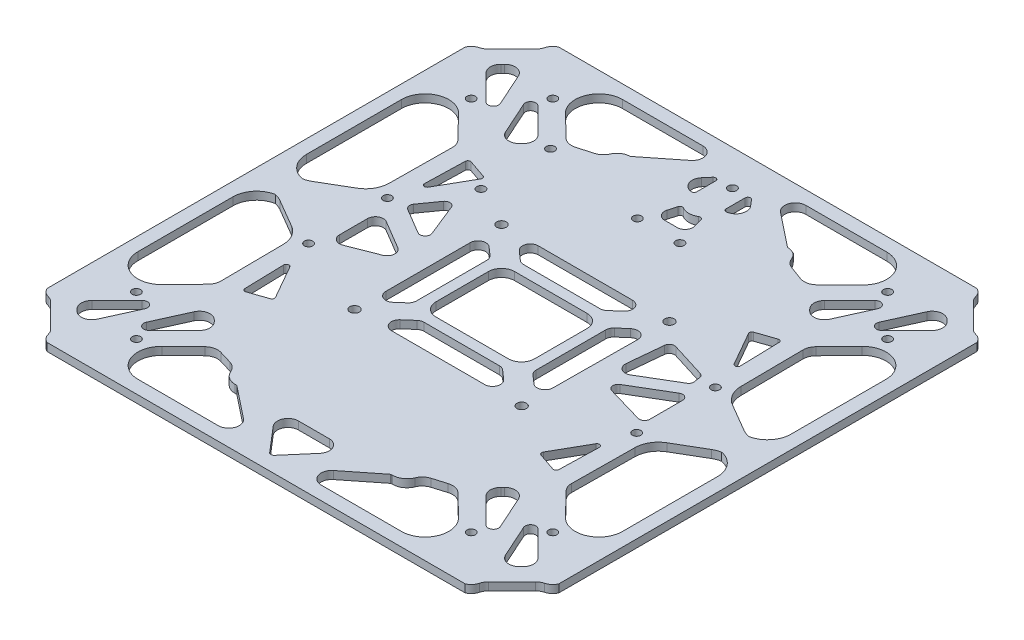
SolidWorks part; units mm, degrees
material "Thornel Mat VMA"
ref_plane "Front Plane" through (0, 0, 0) normal (0, 0, 1) x (1, 0, 0)
ref_plane "Top Plane" through (0, 0, 0) normal (0, 1, 0) x (1, 0, 0)
ref_plane "Right Plane" through (0, 0, 0) normal (1, 0, 0) x (0, 0, -1)
sketch "Sketch2" plane through (0, 0, 0) normal (0, 1, 0) x (1, 0, 0)
  line L1 (-97.5, -97.5) -> (97.5, -97.5)
  line L2 (-97.5, -97.5) -> (-97.5, 97.5)
  line L3 (-97.5, 97.5) -> (97.5, 97.5)
  line L4 (97.5, -97.5) -> (97.5, 97.5)
  line L5 (-97.5, -97.5) -> (97.5, 97.5) construction
  line L6 (-97.5, 97.5) -> (97.5, -97.5) construction
  point P0 (0, 0)
  dimension "D1" = 195
  dimension "D2" = 195
extrude "Boss-Extrude1" add sketch "Sketch2" along normal blind 3
sketch "Sketch3" plane through (0, 3, 0) normal (0, 1, 0) x (1, 0, 0)
  circle A2 centre (47.5, 41.25) radius 1.6
  circle A3 centre (47.5, -41.25) radius 1.6
  circle A4 centre (-47.5, -41.25) radius 1.6
  circle A5 centre (-47.5, 41.25) radius 1.6
  dimension "D3" = 3.2
extrude "Cut-Extrude1" cut sketch "Sketch3" against normal through all both and the other way through all
sketch "Sketch4" plane through (0, 3, 0) normal (0, 1, 0) x (1, 0, 0)
  line L4 (97.5, 97.5) -> (-97.5, 97.5) construction
  circle A0 centre (46.1238, 61.6802) radius 2.11
  circle A3 centre (-61.6802, 46.1238) radius 2.11
  circle A5 centre (-77.9437, 93.5) radius 1.35
  circle A6 centre (-93.5, 77.9437) radius 1.35
  circle A7 centre (-46.1238, 61.6802) radius 2.11
  circle A8 centre (93.5, 77.9437) radius 1.35
  circle A9 centre (77.9437, 93.5) radius 1.35
  circle A10 centre (61.6802, 46.1238) radius 2.11
  circle A11 centre (61.6802, -46.1238) radius 2.11
  circle A12 centre (77.9437, -93.5) radius 1.35
  circle A13 centre (93.5, -77.9437) radius 1.35
  circle A14 centre (-46.1238, -61.6802) radius 2.11
  circle A15 centre (-93.5, -77.9437) radius 1.35
  circle A16 centre (-77.9437, -93.5) radius 1.35
  circle A17 centre (-61.6802, -46.1238) radius 2.11
  circle A18 centre (46.1238, -61.6802) radius 2.11
  dimension "D1" = 2.7
  dimension "D3" = 4.22
  dimension "D6" = 4
extrude "Cut-Extrude2" cut sketch "Sketch4" against normal through all both and the other way through all
sketch "Sketch5" plane through (0, 3, 0) normal (0, 1, 0) x (1, 0, 0)
  circle A1 centre (30, 70) radius 2
  circle A2 centre (15, 70) radius 2
  circle A3 centre (-15, 70) radius 2
  circle A4 centre (-30, 70) radius 2
  circle A5 centre (-30, -70) radius 2
  circle A6 centre (-15, -70) radius 2
  circle A7 centre (15, -70) radius 2
  circle A8 centre (30, -70) radius 2
  dimension "D3" = 4
  dimension "D4" = 4
  dimension "D1" = 4
  dimension "D2" = 4
  dimension "D5" = 4
  dimension "D6" = 4
  dimension "D7" = 4
  dimension "D8" = 4
extrude "Cut-Extrude3" cut sketch "Sketch5" against normal through all both and the other way through all
sketch "Sketch6" plane through (0, 3, 0) normal (0, 1, 0) x (1, 0, 0)
  circle A2 centre (-62.5, 15) radius 1.6
  circle A3 centre (-62.5, -15) radius 1.6
  circle A4 centre (62.5, -15) radius 1.6
  circle A5 centre (62.5, 15) radius 1.6
  dimension "D2" = 3.2
extrude "Cut-Extrude4" cut sketch "Sketch6" against normal through all both and the other way through all
sketch "Sketch7" plane through (0, 3, 0) normal (0, 1, 0) x (1, 0, 0)
  line L0 (-68.2257, 47.6002) -> (-92.338, 72.3986)
  line L1 (-92.3432, 83.4505) -> (-83.4505, 92.3432)
  line L2 (-72.3986, 92.338) -> (-48.2358, 68.8437)
  line L3 (-43.3841, 67.6187) -> (-37.7917, 69.2071)
  line L4 (-67.1, 15) -> (-66.8107, 44.0648)
  line L5 (-30, 75) -> (-15, 75)
  line L6 (-15, 75) -> (15, 75)
  line L7 (15, 75) -> (30, 75)
  line L8 (37.5401, 69.065) -> (42.7993, 67.1289)
  line L9 (48.04, 68.2636) -> (72.4199, 92.3408)
  line L10 (83.4505, 92.3432) -> (92.3432, 83.4505)
  line L11 (68.2257, 47.6002) -> (92.338, 72.3986)
  line L12 (66.8107, 44.0648) -> (67.1, 15)
  line L13 (-67.1, -15) -> (-67.0991, 15.0916)
  line L14 (66.8107, -44.0648) -> (67.1, -15)
  line L15 (68.2257, -47.6002) -> (92.338, -72.3986)
  line L16 (83.4505, -92.3432) -> (92.3432, -83.4505)
  line L17 (48.2358, -68.8437) -> (72.3986, -92.338)
  line L18 (38.2846, -69.1587) -> (43.3041, -67.6421)
  line L19 (15, -75.5) -> (30, -75.5)
  line L20 (-15, -75.5) -> (15, -75.5)
  line L21 (-30, -75.5) -> (-15, -75.5)
  line L22 (-67.1, -15) -> (-66.8107, -44.0648)
  line L23 (-43.3041, -67.6421) -> (-38.2846, -69.1587)
  line L24 (-72.3986, -92.338) -> (-48.2358, -68.8437)
  line L25 (-92.3432, -83.4505) -> (-83.4505, -92.3432)
  line L26 (-68.2257, -47.6002) -> (-92.338, -72.3986)
  line L27 (67.0991, -15.0916) -> (67.1, 15)
  line L29 (-123.1678, -119.5363) -> (123.1678, -119.5363)
  line L30 (-123.1678, -119.5363) -> (-123.1678, 119.5363)
  line L31 (-123.1678, 119.5363) -> (123.1678, 119.5363)
  line L32 (123.1678, -119.5363) -> (123.1678, 119.5363)
  line L33 (-123.1678, -119.5363) -> (123.1678, 119.5363) construction
  line L34 (-123.1678, 119.5363) -> (123.1678, -119.5363) construction
  arc A0 (68.2257, 47.6002) -> (66.8107, 44.0648) centre (71.8104, 44.1146) ccw
  arc A1 (42.7993, 67.1289) -> (48.04, 68.2636) centre (44.5266, 71.8211) ccw
  arc A2 (37.5401, 69.065) -> (34.6337, 71.8786) centre (39.2674, 73.7571) cw
  arc A3 (-37.7917, 69.2071) -> (-34.5789, 72.0084) centre (-39.1578, 74.0168) ccw
  arc A4 (-48.2358, 68.8437) -> (-43.3841, 67.6187) centre (-44.7502, 72.4285) ccw
  arc A5 (-66.8107, 44.0648) -> (-68.2257, 47.6002) centre (-71.8104, 44.1146) ccw
  arc A6 (-92.338, 72.3986) -> (-94.6272, 73.7422) centre (-95.9228, 68.913) ccw
  arc A7 (-72.3986, 92.338) -> (-73.7422, 94.6272) centre (-68.913, 95.9228) cw
  arc A8 (-82.1505, 94.6067) -> (-83.4505, 92.3432) centre (-86.986, 95.8787) cw
  arc A9 (-92.3432, 83.4505) -> (-94.6067, 82.1505) centre (-95.8787, 86.986) cw
  arc A10 (92.338, 72.3986) -> (94.6272, 73.7422) centre (95.9228, 68.913) cw
  circle A11 centre (-93.5, 77.9437) radius 4.35
  arc A12 (-94.6067, 82.1505) -> (-94.6272, 73.7422) centre (-93.5, 77.9437) ccw
  arc A13 (92.3432, 83.4505) -> (94.6067, 82.1505) centre (95.8787, 86.986) ccw
  arc A14 (83.4505, 92.3432) -> (82.1505, 94.6067) centre (86.986, 95.8787) cw
  arc A15 (72.4199, 92.3408) -> (73.7392, 94.6158) centre (68.9065, 95.8983) ccw
  arc A16 (67.1, -15) -> (67.0991, -15.0916) centre (62.5, -15) cw
  arc A17 (-67.0991, -15.0916) -> (-67.1, -15) centre (-62.5, -15) cw
  arc A18 (94.6272, -73.7422) -> (94.6067, -82.1505) centre (93.5, -77.9437) cw
  arc A19 (82.1505, -94.6067) -> (73.7422, -94.6272) centre (77.9437, -93.5) cw
  arc A20 (35.097, -72.0664) -> (30, -75.5) centre (30, -70) cw
  circle A21 centre (-77.9437, 93.5) radius 4.35
  arc A22 (-73.7422, 94.6272) -> (-82.1505, 94.6067) centre (-77.9437, 93.5) ccw
  arc A23 (-30, -75.5) -> (-35.097, -72.0664) centre (-30, -70) cw
  arc A24 (-73.7422, -94.6272) -> (-82.1505, -94.6067) centre (-77.9437, -93.5) cw
  arc A25 (72.3986, -92.338) -> (73.7422, -94.6272) centre (68.913, -95.9228) cw
  arc A26 (83.4505, -92.3432) -> (82.1505, -94.6067) centre (86.986, -95.8787) ccw
  arc A27 (92.3432, -83.4505) -> (94.6067, -82.1505) centre (95.8787, -86.986) cw
  arc A28 (-94.6067, -82.1505) -> (-94.6272, -73.7422) centre (-93.5, -77.9437) cw
  arc A29 (92.338, -72.3986) -> (94.6272, -73.7422) centre (95.9228, -68.913) ccw
  arc A30 (-92.3432, -83.4505) -> (-94.6067, -82.1505) centre (-95.8787, -86.986) ccw
  arc A31 (-82.1505, -94.6067) -> (-83.4505, -92.3432) centre (-86.986, -95.8787) ccw
  arc A32 (-72.3986, -92.338) -> (-73.7422, -94.6272) centre (-68.913, -95.9228) ccw
  arc A33 (-92.338, -72.3986) -> (-94.6272, -73.7422) centre (-95.9228, -68.913) cw
  arc A34 (-66.8107, -44.0648) -> (-68.2257, -47.6002) centre (-71.8104, -44.1146) cw
  arc A36 (-48.2358, -68.8437) -> (-43.3041, -67.6421) centre (-44.7502, -72.4285) cw
  arc A38 (-38.2846, -69.1587) -> (-35.097, -72.0664) centre (-39.7307, -73.945) cw
  arc A39 (38.2846, -69.1587) -> (35.097, -72.0664) centre (39.7307, -73.945) ccw
  arc A43 (43.3041, -67.6421) -> (48.2358, -68.8437) centre (44.7502, -72.4285) cw
  arc A44 (68.2257, -47.6002) -> (66.8107, -44.0648) centre (71.8104, -44.1146) cw
  circle A56 centre (-30, 70) radius 5
  arc A57 (-30, 75) -> (-34.5789, 72.0084) centre (-30, 70) ccw
  circle A65 centre (30, 70) radius 5
  arc A66 (34.6337, 71.8786) -> (30, 75) centre (30, 70) ccw
  circle A74 centre (77.9437, 93.5) radius 4.35
  arc A75 (82.1505, 94.6067) -> (73.7392, 94.6158) centre (77.9437, 93.5) ccw
  circle A77 centre (93.5, 77.9437) radius 4.35
  arc A78 (94.6272, 73.7422) -> (94.6067, 82.1505) centre (93.5, 77.9437) ccw
  circle A85 centre (-62.5, 15) radius 4.6
  arc A86 (-67.0991, 15.0916) -> (-67.1, 15) centre (-62.5, 15) ccw
  circle A88 centre (62.5, 15) radius 4.6
  arc A89 (67.1, 15) -> (67.0991, 15.0916) centre (62.5, 15) ccw
  point P16 (35, 70)
  point P24 (-35, 70)
  point P39 (-93.5, 73.5937)
  point P42 (-73.5937, 93.5)
  point P53 (-82.2937, 93.5)
  point P58 (-93.5, 82.2937)
  point P61 (93.5, 73.5937)
  point P69 (93.5, 82.2937)
  point P72 (82.2937, 93.5)
  point P75 (73.5937, 93.5)
  point P76 (0, 0)
  line M55 (97.5, -97.5) -> (97.5, 97.5)
  line M56 (97.5, 97.5) -> (-97.5, 97.5)
  line M57 (-97.5, 97.5) -> (-97.5, -97.5)
  line M58 (-97.5, -97.5) -> (97.5, -97.5)
  dimension "D3" = 5
  dimension "D4" = 5
  dimension "D1" = 3
  dimension "D2" = 3
  dimension "D5" = 3
  dimension "D6" = 3
  dimension "D8" = 3
  dimension "D11" = 3
  dimension "D14" = 3
  dimension "D15" = 3
extrude "Cut-Extrude5" cut sketch "Sketch7" against normal through all both and the other way through all contours A86 L4 A5 L0 A6 A12 A28 A33 L26 A34 L22 A17 L13 M57 | A24 A31 L25 A30 A28 M57 M58 | L29 L32 L31 L30 A78 A18 A19 A24 A28 A12 A22 A75 M55 M58 M57 M56 | A43 L18 A39 A20 L19 L20 L21 A23 A38 L23 A36 L24 A32 A24 A19 A25 L17 M58 | A89 L27 L14 A16 A44 L15 A29 A18 A78 A10 L11 A0 L12 M55 | A27 L16 A26 A19 A18 M58 M55 | A75 A22 A7 L2 A4 L3 A3 A57 L5 L6 L7 A66 A2 L8 A1 L9 A15 M56 | A22 A12 A9 L1 A8 M56 M57 | A78 A75 A14 L10 A13 M55 M56 region at (-83.5018, 3, 0) region at (-91.2706, 3, -91.2706) region at (-91.2706, 3, 91.2706) region at (0.1643, 3, -85.7939) region at (0, 3, 85.9801) region at (91.2706, 3, -91.2706) region at (91.2706, 3, 91.2706) region at (83.5018, 3, 0) region at (-119.7351, 3, 0) body kept at (-79.6532, 0, 97.5)
sketch "Sketch8" plane through (0, 3, 0) normal (0, 1, 0) x (1, 0, 0)
  line L14 (-46.0759, -21.349) -> (-46.0759, 21.3635)
  line L23 (56.1243, 4.2494) -> (47.983, 21.7846)
  line L24 (-47.9835, -21.7689) -> (-56.1299, -4.1605)
  line L25 (-56.1243, 4.2494) -> (-47.983, 21.7846)
  line L26 (47.9835, -21.7689) -> (56.1299, -4.1605)
  line L27 (46.0759, -21.349) -> (46.0759, 21.3635)
  line L30 (-58.3187, 26.3483) -> (-51.0349, 39.095)
  line L31 (-51.5781, 40.5368) -> (-58.4638, 42.9035)
  line L32 (-59.7885, 41.9842) -> (-60.1866, 26.8708)
  line L33 (-59.7885, -41.9842) -> (-60.1866, -26.8708)
  line L35 (59.7885, 41.9842) -> (60.1866, 26.8708)
  line L36 (51.5781, 40.5368) -> (58.4638, 42.9035)
  line L37 (58.3187, 26.3483) -> (51.0349, 39.095)
  line L38 (-51.5781, -40.5368) -> (-58.4638, -42.9035)
  line L39 (-58.3187, -26.3483) -> (-51.0349, -39.095)
  line L40 (58.3187, -26.3483) -> (51.0349, -39.095)
  line L41 (51.5781, -40.5368) -> (58.4638, -42.9035)
  line L42 (59.7885, -41.9842) -> (60.1866, -26.8708)
  line L43 (-29.1909, -41.25) -> (-22, -41.25)
  line L44 (-15, -48.25) -> (-15, -58)
  line L46 (-22, -65) -> (-23.2561, -65)
  line L47 (-29.2355, -61.6396) -> (-35.1703, -51.8896)
  line L48 (29.1909, 41.25) -> (22, 41.25)
  line L50 (29.2355, -61.6396) -> (35.1703, -51.8896)
  line L51 (22, -65) -> (23.2561, -65)
  line L52 (15, -48.25) -> (15, -58)
  line L53 (29.1909, -41.25) -> (22, -41.25)
  line L54 (15, 48.25) -> (15, 58)
  line L55 (22, 65) -> (23.2561, 65)
  line L56 (29.2355, 61.6396) -> (35.1703, 51.8896)
  line L57 (-29.2355, 61.6396) -> (-35.1703, 51.8896)
  line L58 (-22, 65) -> (-23.2561, 65)
  line L59 (-15, 48.25) -> (-15, 58)
  line L60 (-29.1909, 41.25) -> (-22, 41.25)
  line L64 (-55.3178, 58.1431) -> (-54.6091, 58.8518)
  line L65 (-54.6091, 64.5086) -> (-64.2157, 74.1152)
  line L66 (-84.3061, 81.4807) -> (-85.0147, 80.7721)
  line L67 (-85.0147, 75.1152) -> (-75.4082, 65.5087)
  line L68 (55.3178, -58.1431) -> (54.6091, -58.8518)
  line L69 (-77.8313, 80.2967) -> (-72.1708, 67.7451)
  line L70 (-67.453, 71.8787) -> (-61.7925, 59.3271)
  line L71 (-32.5, -18.2077) -> (-14.5052, -3.0601)
  line L72 (67.453, 71.8787) -> (61.7925, 59.3271)
  line L73 (77.8313, 80.2967) -> (72.1708, 67.7451)
  line L74 (85.0147, 75.1152) -> (75.4082, 65.5087)
  line L75 (84.3061, 81.4807) -> (85.0147, 80.7721)
  line L76 (54.6091, 64.5086) -> (64.2157, 74.1152)
  line L77 (55.3178, 58.1431) -> (54.6091, 58.8518)
  line L78 (54.6091, -64.5086) -> (64.2157, -74.1152)
  line L79 (84.3061, -81.4807) -> (85.0147, -80.7721)
  line L80 (85.0147, -75.1152) -> (75.4082, -65.5087)
  line L81 (77.8313, -80.2967) -> (72.1708, -67.7451)
  line L82 (67.453, -71.8787) -> (61.7925, -59.3271)
  line L83 (-67.453, -71.8787) -> (-61.7925, -59.3271)
  line L84 (-77.8313, -80.2967) -> (-72.1708, -67.7451)
  line L85 (-85.0147, -75.1152) -> (-75.4082, -65.5087)
  line L86 (-84.3061, -81.4807) -> (-85.0147, -80.7721)
  line L87 (-54.6091, -64.5086) -> (-64.2157, -74.1152)
  line L88 (-55.3178, -58.1431) -> (-54.6091, -58.8518)
  line L89 (-32.5, 18.2077) -> (-14.5052, 3.0601)
  line L90 (-39.0759, -15.1476) -> (-39.0759, 15.1476)
  line L91 (-20.3144, 26.25) -> (-2.5759, 11.3182)
  line L92 (2.5759, 11.3182) -> (20.3144, 26.25)
  line L93 (-17.7385, 33.3101) -> (17.7385, 33.3101)
  line L94 (32.5, -18.2077) -> (14.5052, -3.0601)
  line L95 (39.0759, 15.1476) -> (39.0759, -15.1476)
  line L96 (14.5052, 3.0601) -> (32.5, 18.2077)
  line L97 (17.7385, -33.3101) -> (-17.7385, -33.3101)
  line L98 (-20.3144, -26.25) -> (-2.5759, -11.3182)
  line L99 (20.3144, -26.25) -> (2.5759, -11.3182)
  circle A13 centre (0, 0) radius 3
  arc A14 (-46.0759, -21.349) -> (-47.9835, -21.7689) centre (-47.0759, -21.349) cw
  arc A15 (-46.0759, 21.3635) -> (-47.983, 21.7846) centre (-47.0759, 21.3635) ccw
  arc A16 (-56.1299, -4.1605) -> (-56.1243, 4.2494) centre (-47.0542, 0.0383) cw
  arc A17 (56.1299, -4.1605) -> (56.1243, 4.2494) centre (47.0542, 0.0383) ccw
  arc A18 (46.0759, 21.3635) -> (47.983, 21.7846) centre (47.0759, 21.3635) cw
  arc A19 (46.0759, -21.349) -> (47.9835, -21.7689) centre (47.0759, -21.349) ccw
  arc A20 (-58.3187, 26.3483) -> (-60.1866, 26.8708) centre (-59.187, 26.8445) cw
  arc A21 (-51.0349, 39.095) -> (-51.5781, 40.5368) centre (-51.9032, 39.5911) ccw
  arc A22 (-58.4638, 42.9035) -> (-59.7885, 41.9842) centre (-58.7889, 41.9578) ccw
  arc A23 (58.4638, 42.9035) -> (59.7885, 41.9842) centre (58.7889, 41.9578) cw
  arc A24 (51.0349, 39.095) -> (51.5781, 40.5368) centre (51.9032, 39.5911) cw
  arc A25 (58.3187, 26.3483) -> (60.1866, 26.8708) centre (59.187, 26.8445) ccw
  arc A26 (-58.4638, -42.9035) -> (-59.7885, -41.9842) centre (-58.7889, -41.9578) cw
  arc A27 (-51.0349, -39.095) -> (-51.5781, -40.5368) centre (-51.9032, -39.5911) cw
  arc A28 (-58.3187, -26.3483) -> (-60.1866, -26.8708) centre (-59.187, -26.8445) ccw
  arc A29 (58.3187, -26.3483) -> (60.1866, -26.8708) centre (59.187, -26.8445) cw
  arc A30 (51.0349, -39.095) -> (51.5781, -40.5368) centre (51.9032, -39.5911) ccw
  arc A31 (58.4638, -42.9035) -> (59.7885, -41.9842) centre (58.7889, -41.9578) ccw
  arc A32 (-15, -48.25) -> (-22, -41.25) centre (-22, -48.25) ccw
  arc A33 (-29.1909, -41.25) -> (-35.1703, -51.8896) centre (-29.1909, -48.25) ccw
  arc A34 (-29.2355, -61.6396) -> (-23.2561, -65) centre (-23.2561, -58) ccw
  arc A35 (-15, -58) -> (-22, -65) centre (-22, -58) cw
  arc A36 (15, -58) -> (22, -65) centre (22, -58) ccw
  arc A37 (29.2355, -61.6396) -> (23.2561, -65) centre (23.2561, -58) cw
  arc A38 (29.1909, -41.25) -> (35.1703, -51.8896) centre (29.1909, -48.25) cw
  arc A39 (15, -48.25) -> (22, -41.25) centre (22, -48.25) cw
  arc A40 (15, 48.25) -> (22, 41.25) centre (22, 48.25) ccw
  arc A41 (29.1909, 41.25) -> (35.1703, 51.8896) centre (29.1909, 48.25) ccw
  arc A42 (29.2355, 61.6396) -> (23.2561, 65) centre (23.2561, 58) ccw
  arc A43 (15, 58) -> (22, 65) centre (22, 58) cw
  arc A44 (-15, 58) -> (-22, 65) centre (-22, 58) ccw
  arc A45 (-29.2355, 61.6396) -> (-23.2561, 65) centre (-23.2561, 58) cw
  arc A46 (-29.1909, 41.25) -> (-35.1703, 51.8896) centre (-29.1909, 48.25) cw
  arc A47 (-15, 48.25) -> (-22, 41.25) centre (-22, 48.25) cw
  arc A48 (-55.3178, 58.1431) -> (-61.7925, 59.3271) centre (-58.1462, 60.9716) cw
  arc A49 (-54.6091, 58.8518) -> (-54.6091, 64.5086) centre (-57.4376, 61.6802) ccw
  arc A50 (-77.8313, 80.2967) -> (-84.3061, 81.4807) centre (-81.4777, 78.6523) ccw
  arc A51 (-85.0147, 80.7721) -> (-85.0147, 75.1152) centre (-82.1863, 77.9437) ccw
  arc A52 (-64.2157, 74.1152) -> (-67.453, 71.8787) centre (-65.6299, 72.7009) ccw
  arc A53 (-72.1708, 67.7451) -> (-75.4082, 65.5087) centre (-73.994, 66.9229) cw
  arc A54 (72.1708, 67.7451) -> (75.4082, 65.5087) centre (73.994, 66.9229) ccw
  arc A55 (64.2157, 74.1152) -> (67.453, 71.8787) centre (65.6299, 72.7009) cw
  arc A56 (85.0147, 80.7721) -> (85.0147, 75.1152) centre (82.1863, 77.9437) cw
  arc A57 (77.8313, 80.2967) -> (84.3061, 81.4807) centre (81.4777, 78.6523) cw
  arc A58 (54.6091, 58.8518) -> (54.6091, 64.5086) centre (57.4376, 61.6802) cw
  arc A59 (55.3178, 58.1431) -> (61.7925, 59.3271) centre (58.1462, 60.9716) ccw
  arc A60 (55.3178, -58.1431) -> (61.7925, -59.3271) centre (58.1462, -60.9716) cw
  arc A61 (54.6091, -58.8518) -> (54.6091, -64.5086) centre (57.4376, -61.6802) ccw
  arc A62 (77.8313, -80.2967) -> (84.3061, -81.4807) centre (81.4777, -78.6523) ccw
  arc A63 (85.0147, -80.7721) -> (85.0147, -75.1152) centre (82.1863, -77.9437) ccw
  arc A64 (64.2157, -74.1152) -> (67.453, -71.8787) centre (65.6299, -72.7009) ccw
  arc A65 (72.1708, -67.7451) -> (75.4082, -65.5087) centre (73.994, -66.9229) cw
  arc A66 (-72.1708, -67.7451) -> (-75.4082, -65.5087) centre (-73.994, -66.9229) ccw
  arc A67 (-64.2157, -74.1152) -> (-67.453, -71.8787) centre (-65.6299, -72.7009) cw
  arc A68 (-85.0147, -80.7721) -> (-85.0147, -75.1152) centre (-82.1863, -77.9437) cw
  arc A69 (-77.8313, -80.2967) -> (-84.3061, -81.4807) centre (-81.4777, -78.6523) cw
  arc A70 (-54.6091, -58.8518) -> (-54.6091, -64.5086) centre (-57.4376, -61.6802) cw
  arc A71 (-55.3178, -58.1431) -> (-61.7925, -59.3271) centre (-58.1462, -60.9716) ccw
  arc A84 (-20.3144, 26.25) -> (-17.7385, 33.3101) centre (-17.7385, 29.3101) cw
  arc A85 (-2.5759, 11.3182) -> (2.5759, 11.3182) centre (0, 14.3784) ccw
  arc A86 (20.3144, 26.25) -> (17.7385, 33.3101) centre (17.7385, 29.3101) ccw
  arc A87 (39.0759, 15.1476) -> (32.5, 18.2077) centre (35.0759, 15.1476) ccw
  arc A88 (14.5052, -3.0601) -> (14.5052, 3.0601) centre (17.0811, 0) cw
  arc A89 (32.5, -18.2077) -> (39.0759, -15.1476) centre (35.0759, -15.1476) ccw
  arc A90 (17.7385, -33.3101) -> (20.3144, -26.25) centre (17.7385, -29.3101) ccw
  arc A91 (-2.5759, -11.3182) -> (2.5759, -11.3182) centre (0, -14.3784) cw
  arc A92 (-17.7385, -33.3101) -> (-20.3144, -26.25) centre (-17.7385, -29.3101) cw
  arc A93 (-32.5, -18.2077) -> (-39.0759, -15.1476) centre (-35.0759, -15.1476) cw
  arc A94 (-14.5052, -3.0601) -> (-14.5052, 3.0601) centre (-17.0811, 0) ccw
  arc A95 (-32.5, 18.2077) -> (-39.0759, 15.1476) centre (-35.0759, 15.1476) ccw
  point P50 (-58.0759, 0.0458)
  point P61 (58.0759, 0.0458)
  dimension "D1" = 4
  dimension "D4" = 1
  dimension "D5" = 10
  dimension "D6" = 1
  dimension "D7" = 7
  dimension "D8" = 4
  dimension "D9" = 2
  dimension "D3" = 12
extrude "Cut-Extrude7" cut sketch "Sketch8" against normal through all both and the other way through all
sketch "Sketch9" plane through (0, 0, 0) normal (0, 1, 0) x (1, 0, 0)
  line L0 (-76.2341, 97.5) -> (76.2341, 97.5)
  line L1 (-97.5, 76.2341) -> (-92.338, 76.2341)
  line L2 (-97.5, 76.2341) -> (-97.5, -76.2341)
  line L3 (-97.5, -76.2341) -> (-92.338, -76.2341)
  line L4 (-92.338, 76.2341) -> (-92.338, -76.2341)
  line L5 (-72.3986, 92.338) -> (75.7801, 92.338)
  line L6 (92.338, 76.2341) -> (92.338, -76.2341)
  line L7 (97.5, -76.2341) -> (92.338, -76.2341)
  line L8 (97.5, 76.2341) -> (97.5, -76.2341)
  line L9 (97.5, 76.2341) -> (92.338, 76.2341)
  line L11 (75.7801, 92.338) -> (76.2341, 97.5)
  line L12 (-76.2341, 97.5) -> (-74.9539, 93.3918)
  line L13 (-74.9539, 93.3918) -> (-72.3986, 92.338)
  line L15 (-74.9539, -93.3918) -> (-72.3986, -92.338)
  line L16 (-76.2341, -97.5) -> (-74.9539, -93.3918)
  line L17 (75.7801, -93.3918) -> (76.2341, -97.5)
  line L18 (72.3986, -92.338) -> (75.7801, -93.3918)
  line L19 (-72.3986, -92.338) -> (72.3986, -92.338)
  line L20 (-76.2341, -97.5) -> (76.2341, -97.5)
extrude "Boss-Extrude2" add sketch "Sketch9" along normal up to surface (3 mm away) up to face at (56.578, 3, 36.2456)
fillet "Fillet1" radius 9 8 edges at (-72.3986, 1.5, 92.338) (-92.338, 1.5, 72.3986) (92.338, 1.5, 72.3986) (72.3986, 1.5, 92.338) (92.338, 1.5, -72.3986) (72.4171, 1.5, -92.338) (-72.3986, 1.5, -92.338) (-92.338, 1.5, -72.3986)
sketch "Sketch10" plane through (0, 0, 0) normal (0, -1, 0) x (1, 0, 0)
  line L0 (0.1317, -92.338) -> (15, -75)
  line L1 (50.4957, -92.338) -> (-50.2322, -92.338) construction
  line L2 (-30, -75) -> (30, -75) construction
  line L3 (15, -75) -> (30, -75)
  line L4 (30, -75) -> (8.1317, -92.338)
  line L5 (8.1317, -92.338) -> (0.1317, -92.338)
  line L7 (-8.1317, -92.338) -> (-0.1317, -92.338)
  line L8 (-30, -75) -> (-8.1317, -92.338)
  line L9 (-15, -75) -> (-30, -75)
  line L10 (-0.1317, -92.338) -> (-15, -75)
  line L11 (-0.1317, 92.338) -> (-15, 75)
  line L12 (-15, 75) -> (-30, 75)
  line L13 (-30, 75) -> (-8.1317, 92.338)
  line L14 (-8.1317, 92.338) -> (-0.1317, 92.338)
  line L15 (8.1317, 92.338) -> (0.1317, 92.338)
  line L16 (30, 75) -> (8.1317, 92.338)
  line L17 (15, 75) -> (30, 75)
  line L18 (0.1317, 92.338) -> (15, 75)
  line L23 (0, 0) -> (0, 24.1776) construction
  line L36 (-92.338, -5) -> (-84.338, -5)
  line L37 (-92.338, 5) -> (-84.338, 5)
  line L38 (-84.338, 5) -> (-67.0991, 15.0916)
  line L39 (-67.0991, 15.0916) -> (-67.0991, -15.0916)
  line L40 (-67.0991, -15.0916) -> (-84.338, -5)
  line L41 (-92.338, 5) -> (-92.338, -5)
  line L42 (92.338, 5) -> (92.338, -5)
  line L43 (67.0991, -15.0916) -> (84.338, -5)
  line L44 (67.0991, 15.0916) -> (67.0991, -15.0916)
  line L45 (84.338, 5) -> (67.0991, 15.0916)
  line L46 (92.338, 5) -> (84.338, 5)
  line L47 (92.338, -5) -> (84.338, -5)
  dimension "D1" = 8
extrude "Boss-Extrude3" add sketch "Sketch10" against normal up to surface (3 mm away) contours L7 L10 L9 L8 | L5 L4 L3 L0 | L39 | L15 L18 L17 L16 | L14 L13 L12 L11 | L41 L36 L40 L39 L38 L37 | L42 L47 L43 L44 L45 L46 region at (14.2476, 0, -82.7895) region at (-14.2476, 0, -82.7895) region at (-14.2476, 0, 82.7895) region at (14.2476, 0, 82.7895) up to face at (0, 3, 74.8987)
fillet "Fillet2" radius 9 12 edges at (84.338, 1.5, 5) (92.338, 1.5, 5) (67.0991, 1.5, 15.0916) (84.338, 1.5, -5) (92.338, 1.5, -5) (67.0991, 1.5, -15.0916) (-84.338, 1.5, 5) (-92.338, 1.5, 5) (-84.338, 1.5, -5) (-92.338, 1.5, -5) (-67.0991, 1.5, -15.0916) (-67.0991, 1.5, 15.0916)
fillet "Fillet3" radius 4 8 edges at (14.5712, 1.5, 75.5) (-14.5712, 1.5, 75.5) (-8.1317, 1.5, 92.338) (8.1317, 1.5, 92.338) (-15, 1.5, -75) (15, 1.5, -75) (8.1317, 1.5, -92.338) (-8.1317, 1.5, -92.338)
sketch "Sketch11" plane through (0, 0, 0) normal (0, -1, 0) x (1, 0, 0)
  line L0 (-1.5025, 92.338) -> (1.4975, 92.338)
  line L1 (-1.5025, 91.838) -> (-1.5025, 90.838) construction
  line L2 (0, 0) -> (117.3836, 0) construction
  line L3 (1.4975, 91.838) -> (1.4975, 90.838) construction
  line L4 (-2.0025, 92.338) -> (1.9975, 92.338) construction
  line L5 (-1.5025, -92.338) -> (-1.5025, -90.838)
  line L6 (1.4975, 92.338) -> (1.4975, 90.838)
  line L7 (1.4975, -92.338) -> (1.4975, -90.838)
  line L8 (-1.5025, 92.338) -> (-1.5025, 90.838)
  line L9 (-1.5025, 91.838) -> (1.4975, 91.838) construction
  line L10 (-2.0025, 92.338) -> (-2.0025, 90.838) construction
  line L11 (-1.5025, -92.338) -> (1.4975, -92.338)
  line L14 (1.9975, 92.338) -> (1.9975, 90.838) construction
  arc A0 (-1.5025, 90.838) -> (1.4975, 90.838) centre (-0.0025, 90.1655) cw
  arc A1 (-1.5025, -90.838) -> (1.4975, -90.838) centre (-0.0025, -90.1655) ccw
  point P3 (-0.0025, 92.338)
  point P19 (-0.0025, -92.338)
  dimension "D4" = 0.5
extrude "Boss-Extrude4" add sketch "Sketch11" against normal up to surface (3 mm away) up to face at (78.3031, 3, -28.8709)
sketch "Sketch12" plane through (0, 0, 0) normal (0, 1, 0) x (1, 0, 0)
  line L1 (-34.1125, -65.173) -> (33.0728, -65.173)
  line L2 (-34.1125, -65.173) -> (-34.1125, -72.502)
  line L3 (-34.1125, -72.502) -> (33.0728, -72.502)
  line L4 (33.0728, -65.173) -> (33.0728, -72.502)
  line L5 (-32.7348, 74.1858) -> (33.0728, 74.1858)
  line L6 (-32.7348, 74.1858) -> (-32.7348, 66.5049)
  line L7 (-32.7348, 66.5049) -> (33.0728, 66.5049)
  line L8 (33.0728, 74.1858) -> (33.0728, 66.5049)
  arc A0 (-30, 75) -> (-34.5789, 72.0084) centre (-30, 70) ccw construction
extrude "Boss-Extrude5" add sketch "Sketch12" along normal up to surface (3 mm away) up to face at (0.0007, 3, 82.7847)
sketch "Sketch13" plane through (0, 3, 0) normal (0, 1, 0) x (1, 0, 0)
  line L0 (-97.5, 79.6532) -> (-97.5, -79.6532) construction
  circle A0 centre (-62.5, 9) radius 1.6
  circle A3 centre (-62.5, 15) radius 1.6 construction
  circle A4 centre (-62.5, -9) radius 1.6
  circle A5 centre (62.5, -9) radius 1.6
  circle A6 centre (62.5, 9) radius 1.6
  dimension "D1" = 3.2
  dimension "D2" = 35
  dimension "D3" = 6
extrude "Cut-Extrude8" cut sketch "Sketch13" against normal through all both and the other way through all
sketch "Sketch14" plane through (0, 3, 0) normal (0, 1, 0) x (1, 0, 0)
  line L1 (-49.7531, -38.4774) -> (-42.6685, -38.4774)
  line L2 (-49.7531, -38.4774) -> (-49.7531, -44.7981)
  line L3 (-49.7531, -44.7981) -> (-42.6685, -44.7981)
  line L4 (-42.6685, -38.4774) -> (-42.6685, -44.7981)
  line L5 (43.2252, -37.3262) -> (50.4701, -37.3262)
  line L6 (43.2252, -37.3262) -> (43.2252, -44.7981)
  line L7 (43.2252, -44.7981) -> (50.4701, -44.7981)
  line L8 (50.4701, -37.3262) -> (50.4701, -44.7981)
  line L9 (-49.7531, 45.318) -> (-42.6685, 45.318)
  line L10 (-49.7531, 45.318) -> (-49.7531, 37.98)
  line L11 (-49.7531, 37.98) -> (-42.6685, 37.98)
  line L12 (-42.6685, 45.318) -> (-42.6685, 37.98)
  line L13 (43.2252, 45.318) -> (50.4701, 45.318)
  line L14 (43.2252, 45.318) -> (43.2252, 35.8323)
  line L15 (43.2252, 35.8323) -> (50.4701, 35.8323)
  line L16 (50.4701, 45.318) -> (50.4701, 35.8323)
extrude "Boss-Extrude6" add sketch "Sketch14" against normal up to surface (3 mm away) up to face at (62.5, 0, -10.6)
sketch "Sketch15" plane through (0, 0, 0) normal (0, 1, 0) x (1, 0, 0)
  line L1 (38.1112, -67.172) -> (-38.039, -67.172)
  line L2 (38.1112, -67.172) -> (38.1112, -38.1498)
  line L3 (38.1112, -38.1498) -> (-38.039, -38.1498)
  line L4 (-38.039, -67.172) -> (-38.039, -38.1498)
  line L5 (58.5626, -23.0556) -> (26.3059, -23.0556)
  line L6 (58.5626, -23.0556) -> (58.5626, 24.5465)
  line L7 (58.5626, 24.5465) -> (26.3059, 24.5465)
  line L8 (-57.9373, -23.0556) -> (-57.9373, 24.5465)
  line L9 (26.3059, -35.8956) -> (-27.2465, -35.8956)
  line L10 (26.3059, -35.8956) -> (26.3059, -23.0556)
  line L12 (-27.2465, -35.8956) -> (-27.2465, -23.0556)
  line L13 (26.3059, 38.0129) -> (40.0854, 38.0129)
  line L14 (-41.6524, 38.0129) -> (-27.2465, 38.0129)
  line L15 (-41.6524, 38.0129) -> (-41.6524, 66.5116)
  line L16 (-41.6524, 66.5116) -> (40.0854, 66.5116)
  line L17 (40.0854, 38.0129) -> (40.0854, 66.5116)
  line L18 (-27.2465, -23.0556) -> (-57.9373, -23.0556)
  line L19 (-27.2465, 24.5465) -> (-27.2465, 38.0129)
  line L20 (-27.2465, 24.5465) -> (-57.9373, 24.5465)
  line L21 (26.3059, 24.5465) -> (26.3059, 38.0129)
extrude "Boss-Extrude7" add sketch "Sketch15" along normal up to surface (3 mm away) up to face at (62.5, 3, -10.6)
sketch "Sketch18" plane through (0, 3, 0) normal (0, 1, 0) x (1, 0, 0)
  circle A0 centre (-63.8015, 79.3579) radius 1.6
  circle A2 centre (-77.9437, 93.5) radius 1.35 construction
  circle A3 centre (-79.3579, 63.8015) radius 1.6
  circle A4 centre (79.3579, 63.8015) radius 1.6
  circle A5 centre (63.8015, 79.3579) radius 1.6
  circle A6 centre (63.8015, -79.3579) radius 1.6
  circle A7 centre (79.3579, -63.8015) radius 1.6
  circle A8 centre (-79.3579, -63.8015) radius 1.6
  circle A9 centre (-63.8015, -79.3579) radius 1.6
  dimension "D1" = 3.2
  dimension "D3" = 20
extrude "Cut-Extrude11" cut sketch "Sketch18" against normal through all both and the other way through all
sketch "Sketch19" plane through (0, 0, 0) normal (0, 1, 0) x (1, 0, 0)
  line L1 (-58.9991, 43.8461) -> (-64.2376, 43.8461)
  line L2 (-58.9991, 43.8461) -> (-58.9991, 49.3282)
  line L3 (-58.9991, 49.3282) -> (-64.2376, 49.3282)
  line L4 (-64.2376, 43.8461) -> (-64.2376, 49.3282)
  line L5 (-42.335, 57.5437) -> (-48.8904, 57.5437)
  line L6 (-42.335, 57.5437) -> (-42.335, 64.4311)
  line L7 (-42.335, 64.4311) -> (-48.8904, 64.4311)
  line L8 (-48.8904, 57.5437) -> (-48.8904, 64.4311)
  line L9 (-74.368, 90.6367) -> (-80.0614, 90.6367)
  line L10 (-74.368, 90.6367) -> (-74.368, 95.3541)
  line L11 (-74.368, 95.3541) -> (-80.0614, 95.3541)
  line L12 (-80.0614, 90.6367) -> (-80.0614, 95.3541)
  line L13 (-89.8214, 76.2406) -> (-95.3521, 76.2406)
  line L14 (-89.8214, 76.2406) -> (-89.8214, 79.494)
  line L15 (-89.8214, 79.494) -> (-95.3521, 79.494)
  line L16 (-95.3521, 76.2406) -> (-95.3521, 79.494)
  line L17 (-56.1855, -50.6932) -> (-64.2376, -50.6932)
  line L18 (-56.1855, -50.6932) -> (-56.1855, -43.2388)
  line L19 (-56.1855, -43.2388) -> (-64.2376, -43.2388)
  line L20 (-64.2376, -50.6932) -> (-64.2376, -43.2388)
  line L21 (-42.7063, -64.591) -> (-49.2618, -64.591)
  line L22 (-42.7063, -64.591) -> (-42.7063, -58.6838)
  line L23 (-42.7063, -58.6838) -> (-49.2618, -58.6838)
  line L24 (-49.2618, -64.591) -> (-49.2618, -58.6838)
  line L25 (-75.03, -95.1732) -> (-80.0614, -95.1732)
  line L26 (-75.03, -95.1732) -> (-75.03, -90.8389)
  line L27 (-75.03, -90.8389) -> (-80.0614, -90.8389)
  line L28 (-80.0614, -95.1732) -> (-80.0614, -90.8389)
  line L29 (-90.9596, -79.6594) -> (-95.3239, -79.6594)
  line L30 (-90.9596, -79.6594) -> (-90.9596, -76.0246)
  line L31 (-90.9596, -76.0246) -> (-95.3239, -76.0246)
  line L32 (-95.3239, -79.6594) -> (-95.3239, -76.0246)
  line L33 (80.0901, -95.6543) -> (75.002, -95.6543)
  line L34 (80.0901, -95.6543) -> (80.0901, -90.8389)
  line L35 (80.0901, -90.8389) -> (75.002, -90.8389)
  line L36 (75.002, -95.6543) -> (75.002, -90.8389)
  line L37 (95.4954, -80.3196) -> (90.4781, -80.3196)
  line L38 (95.4954, -80.3196) -> (95.4954, -74.5956)
  line L39 (95.4954, -74.5956) -> (90.4781, -74.5956)
  line L40 (90.4781, -80.3196) -> (90.4781, -74.5956)
  line L41 (66.6023, -49.6041) -> (56.5046, -49.6041)
  line L42 (66.6023, -49.6041) -> (66.6023, -43.2388)
  line L43 (66.6023, -43.2388) -> (56.5046, -43.2388)
  line L44 (56.5046, -49.6041) -> (56.5046, -43.2388)
  line L45 (51.6645, -66.0441) -> (38.3956, -66.0441)
  line L46 (51.6645, -66.0441) -> (51.6645, -55.9464)
  line L47 (51.6645, -55.9464) -> (38.3956, -55.9464)
  line L48 (38.3956, -66.0441) -> (38.3956, -55.9464)
  line L49 (64.9022, 43.2418) -> (56.5046, 43.2418)
  line L50 (64.9022, 43.2418) -> (64.9022, 50.8486)
  line L51 (64.9022, 50.8486) -> (56.5046, 50.8486)
  line L52 (56.5046, 43.2418) -> (56.5046, 50.8486)
  line L53 (51.6645, 57.5437) -> (40.5804, 57.5437)
  line L54 (51.6645, 57.5437) -> (51.6645, 65.6618)
  line L55 (51.6645, 65.6618) -> (40.5804, 65.6618)
  line L56 (40.5804, 57.5437) -> (40.5804, 65.6618)
  line L57 (95.8981, 75.2293) -> (91.1878, 75.2293)
  line L58 (95.8981, 75.2293) -> (95.8981, 80.9683)
  line L59 (95.8981, 80.9683) -> (91.1878, 80.9683)
  line L60 (91.1878, 75.2293) -> (91.1878, 80.9683)
  line L61 (81.0162, 88.7637) -> (73.3933, 88.7637)
  line L62 (81.0162, 88.7637) -> (81.0162, 95.3541)
  line L63 (81.0162, 95.3541) -> (73.3933, 95.3541)
  line L64 (73.3933, 88.7637) -> (73.3933, 95.3541)
  line L65 (-57.6088, -11.5948) -> (-66.4862, -11.5948)
  line L66 (-57.6088, -11.5948) -> (-57.6088, -5.9017)
  line L67 (-57.6088, -5.9017) -> (-66.4862, -5.9017)
  line L68 (-66.4862, -11.5948) -> (-66.4862, -5.9017)
  line L69 (-56.1855, 5.581) -> (-67.7406, 5.581)
  line L70 (-56.1855, 5.581) -> (-56.1855, 11.467)
  line L71 (-56.1855, 11.467) -> (-67.7406, 11.467)
  line L72 (-67.7406, 5.581) -> (-67.7406, 11.467)
  line L73 (68.2553, 4.1425) -> (52.9739, 4.1425)
  line L74 (68.2553, 4.1425) -> (68.2553, 11.467)
  line L75 (68.2553, 11.467) -> (52.9739, 11.467)
  line L76 (52.9739, 4.1425) -> (52.9739, 11.467)
  line L77 (66.6023, -11.5948) -> (57.8413, -11.5948)
  line L78 (66.6023, -11.5948) -> (66.6023, -5.9017)
  line L79 (66.6023, -5.9017) -> (57.8413, -5.9017)
  line L80 (57.8413, -11.5948) -> (57.8413, -5.9017)
extrude "Boss-Extrude8" add sketch "Sketch19" along normal up to surface (3 mm away) up to face at (63.8015, 3, 77.7579)
sketch "Sketch21" plane through (0, 3, 0) normal (0, 1, 0) x (1, 0, 0)
  circle A0 centre (32, 28) radius 1.8
  circle A3 centre (31.6859, -27.9991) radius 1.8
  circle A4 centre (-32, -28) radius 1.8
  circle A5 centre (-32, 28) radius 1.8
  dimension "D2" = 3.6
  dimension "D4" = 3.6
  dimension "D3" = 28
  dimension "D1" = 32
  dimension "D5" = 56
  dimension "D6" = 56
  dimension "D7" = 0
extrude "Cut-Extrude13" cut sketch "Sketch21" against normal through all both and the other way through all
sketch "Sketch22" plane through (0, 3, 0) normal (0, 1, 0) x (1, 0, 0)
  line L1 (-19.6154, 92.338) -> (-50.2322, 92.338) construction
  line L2 (92.338, 14) -> (92.338, 50.2322) construction
  circle A0 centre (-47.662, 62.338) radius 1.6
  circle A1 centre (-47.662, 35.838) radius 1.6
  dimension "D1" = 3.2
  dimension "D2" = 26.5
  dimension "D3" = 30
  dimension "D4" = 140
extrude "Cut-Extrude14" cut sketch "Sketch22" against normal through all both and the other way through all
sketch "Sketch23" plane through (0, 3, 0) normal (0, 1, 0) x (1, 0, 0)
  line L0 (-5.2076, 64.3299) -> (-2.0054, 75.4017)
  line L1 (2.2066, 75.3975) -> (5.3554, 64.3165)
  line L3 (-17.9982, 28) -> (17.9413, 28)
  line L4 (31.9169, 15.9803) -> (31.695, -16.1249)
  line L5 (17.6111, -28) -> (-17.9403, -28)
  line L6 (-32, -16.0736) -> (-32, 16.0332)
  line L7 (2.4724, 60.5) -> (-2.3284, 60.5)
  line L9 (-27.0177, 18.285) -> (-24.0177, 15.6441)
  line L10 (-19.9157, -22.7426) -> (-16.4867, -19.7423)
  line L12 (-27.0248, -18.3312) -> (-24.0248, -15.7062)
  line L15 (-59.5, 4.4594) -> (-59.5, -6.2212)
  line L17 (-55.4104, -9.0163) -> (-44.5518, -4.7832)
  line L20 (-44.1098, 0.5914) -> (-54.9683, 7.0389)
  line L21 (-19.0001, 10.0001) -> (-19.0003, -9.9999)
  line L26 (-19.9804, 22.7482) -> (-16.5725, 19.7482)
  line L31 (-14.0003, -15) -> (13.613, -15)
  line L32 (18.613, 10) -> (18.613, -10)
  line L35 (-14.0001, 15) -> (13.613, 15)
  line L36 (-23, 13.3923) -> (-23.0003, -13.4485)
  line L37 (-14.5112, -19) -> (14.2032, -19)
  line L38 (22.613, 13.11) -> (22.613, -13.391)
  line L39 (-14.5902, 19) -> (14.5127, 19)
  line L40 (-19.0004, -15) -> (18.613, -15) construction
  line L41 (18.613, 15) -> (18.613, -15) construction
  line L42 (-19, 15) -> (18.613, 15) construction
  line L43 (16.1855, -19.7482) -> (19.5937, -22.7485)
  line L44 (23.6307, -15.6428) -> (26.7129, -18.356)
  line L45 (23.6375, 15.3677) -> (26.9415, 18.2587)
  line L46 (16.4882, 19.7423) -> (19.9168, 22.7423)
  line L47 (-19, 15) -> (-19.0004, -15) construction
  line L48 (-22.9999, 19) -> (-23.0004, -19) construction
  line L49 (-22.9999, 19) -> (22.613, 19) construction
  line L50 (-23.0004, -19) -> (22.613, -19) construction
  line L51 (22.613, 19) -> (22.613, -19) construction
  line L55 (57.5, 6.2162) -> (43.3678, -2.1751)
  line L56 (43.831, -5.8154) -> (57.9632, -9.9206)
  line L57 (60.5211, -8) -> (60.5211, 4.4965)
  line L61 (42.2127, 2.954) -> (55.6962, 10.9601)
  line L62 (54.9333, 16.7524) -> (41.5051, 20.9238)
  line L64 (79.6532, 97.5) -> (-79.6532, 97.5) construction
  line L65 (37.6221, 5.8708) -> (38.9212, 19.2077)
  line L67 (-54.852, 15.1108) -> (-45.2027, 9.3813)
  line L68 (-45.7499, 31.6272) -> (-45.8897, 31.4308)
  line L71 (-42.326, 11.8472) -> (-47.281, 24.1692)
  line L72 (-50.7657, 24.5831) -> (-55.46, 17.9906)
  arc A1 (2.4724, 60.5) -> (5.3554, 64.3165) centre (2.4724, 63.4972) ccw
  arc A11 (-0.0622, 76.8459) -> (0.2088, 76.8494) centre (0, 82.5) ccw
  arc A12 (-5.2076, 64.3299) -> (-2.3284, 60.5) centre (-2.3284, 63.4972) ccw
  arc A19 (31.695, -16.1249) -> (26.7129, -18.356) centre (28.6951, -16.1042) cw
  arc A20 (26.9415, 18.2587) -> (31.9169, 15.9803) centre (28.917, 16.001) cw
  arc A21 (19.9168, 22.7423) -> (17.9413, 28) centre (17.9413, 25) ccw
  arc A24 (19.5937, -22.7485) -> (17.6111, -28) centre (17.6111, -25) cw
  arc A26 (-19.9157, -22.7426) -> (-17.9403, -28) centre (-17.9403, -25.0002) ccw
  arc A27 (-32, -16.0736) -> (-27.0248, -18.3312) centre (-29.0002, -16.0736) ccw
  arc A29 (-32, 16.0332) -> (-27.0177, 18.285) centre (-29, 16.0332) cw
  arc A30 (-17.9982, 28) -> (-19.9804, 22.7482) centre (-17.9982, 25) ccw
  arc A31 (0.2088, 76.8494) -> (2.2066, 75.3975) centre (0.2827, 74.8508) cw
  arc A32 (-0.0622, 76.8459) -> (-2.0054, 75.4017) centre (-0.0841, 74.846) ccw
  arc A34 (-44.5518, -4.7832) -> (-44.1098, 0.5914) centre (-45.6414, -1.9881) ccw
  arc A35 (-59.5, -6.2212) -> (-55.4104, -9.0163) centre (-56.5, -6.2212) ccw
  arc A36 (-59.5, 4.4594) -> (-54.9683, 7.0389) centre (-56.5, 4.4594) cw
  arc A37 (13.613, -15) -> (18.613, -10) centre (13.613, -10) ccw
  arc A38 (18.613, 10) -> (13.613, 15) centre (13.613, 10) ccw
  arc A39 (-19.0003, -9.9999) -> (-14.0003, -15) centre (-14.0003, -10) ccw
  arc A40 (-19.0001, 10.0001) -> (-14.0001, 15) centre (-14.0001, 10) cw
  arc A45 (57.9632, -9.9206) -> (60.5211, -8) centre (58.5211, -8) ccw
  arc A46 (57.5, 6.2162) -> (60.5211, 4.4965) centre (58.5211, 4.4965) cw
  arc A47 (43.3678, -2.1751) -> (43.831, -5.8154) centre (44.3889, -3.8948) ccw
  arc A54 (56.3396, 14.881) -> (56.5926, 13.2484) centre (62.5, 15) ccw
  arc A57 (56.3396, 14.881) -> (54.9333, 16.7524) centre (54.3399, 14.8424) ccw
  arc A58 (56.5926, 13.2484) -> (55.6962, 10.9601) centre (54.6751, 12.6798) cw
  arc A65 (37.6221, 5.8708) -> (42.2127, 2.954) centre (40.6563, 5.5753) ccw
  arc A66 (41.5051, 20.9238) -> (38.9212, 19.2077) centre (40.9118, 19.0138) ccw
  circle A68 centre (62.5, -15) radius 1.6 construction
  arc A69 (-42.326, 11.8472) -> (-45.2027, 9.3813) centre (-44.1816, 11.101) cw
  arc A70 (-54.852, 15.1108) -> (-55.46, 17.9906) centre (-53.8309, 16.8305) cw
  arc A71 (-50.7657, 24.5831) -> (-47.281, 24.1692) centre (-49.1366, 23.423) cw
  arc A72 (-16.5725, 19.7482) -> (-14.5902, 19) centre (-14.5902, 22) ccw
  arc A73 (16.4882, 19.7423) -> (14.5127, 19) centre (14.5127, 22) cw
  arc A74 (23.6375, 15.3677) -> (22.613, 13.11) centre (25.613, 13.11) ccw
  arc A75 (23.6307, -15.6428) -> (22.613, -13.391) centre (25.613, -13.391) cw
  arc A76 (16.1855, -19.7482) -> (14.2032, -19) centre (14.2032, -22) ccw
  arc A77 (-16.4867, -19.7423) -> (-14.5112, -19) centre (-14.5112, -22) cw
  arc A78 (-24.0248, -15.7062) -> (-23.0003, -13.4485) centre (-26.0003, -13.4485) ccw
  arc A79 (-24.0177, 15.6441) -> (-23, 13.3923) centre (-26, 13.3923) cw
  point P59 (-0.089, 5.2376)
  point P62 (5.9673, -0.095)
  point P100 (22.613, -14.7469)
  point P115 (-23.0003, -14.8098)
  dimension "D2" = 2
  dimension "D3" = 30
  dimension "D5" = 5
  dimension "D6" = 2
  dimension "D7" = 9
  dimension "D8" = 2
  dimension "D17" = 2
  dimension "D18" = 3
  dimension "D20" = 16.3494
  dimension "D19" = 15
  dimension "D9" = 16.4357
  dimension "D10" = 5
  dimension "D11" = 7
  dimension "D4" = 4
  dimension "D12" = 4
  dimension "D13" = 9
  dimension "D14" = 15
  dimension "D15" = 29.8098
  dimension "D16" = 29.7469
extrude "Cut-Extrude15" cut sketch "Sketch23" against normal through all both and the other way through all contours L10 A26 L5 A24 L43 L37 | A40 L21 A39 L31 A37 L32 A38 L35 | A29 L6 A27 L12 L36 L9 | A20 L45 L38 L44 A19 L4 | L3 A30 L26 L39 L46 A21 | A73 | A70 | A11 A32 L0 A12 L7 A1 L1 A31 | L62 A66 L65 A65 L61 A58 A54 A57 | L55 A47 L56 A45 L57 A46 | A36 L15 A35 L17 A34 L20 | L71 L72 L67 region at (0.081, 3, -67.3579) region at (-0.0307, 3, -23.669) region at (27.3717, 3, 0.0055) region at (-0.1621, 3, 23.6707) region at (-27.6484, 3, 0.022) region at (-52.7618, 3, 1.2006) region at (-0.1936, 3, 0) region at (53.6218, 3, 2.4208) region at (45.6009, 3, -12.2157) region at (-48.7804, 3, -16.9381)
sketch "Sketch24" plane through (0, 0, 0) normal (0, 1, 0) x (1, 0, 0)
  line L2 (-5.6, 73) -> (-5.6, 92.6045)
  line L3 (-5.6, 92.6045) -> (5.6, 92.6045)
  line L4 (5.6, 73) -> (5.6, 92.6045)
  arc A1 (-5.6, 73) -> (5.6, 73) centre (0, 73) ccw
extrude "Boss-Extrude9" add sketch "Sketch24" along normal up to surface (3 mm away) up to face at (-52.9748, 3, 1.3051)
fillet "Fillet4" radius 1 4 edges at (-5.6, 1.5, -85.9614) (-5.6, 1.5, -75) (5.6, 1.5, -75) (5.6, 1.5, -85.9614)
fillet "Fillet5" radius 1 2 edges at (-3.8705, 1.5, -68.9529) (4.0012, 1.5, -69.082)
sketch "Sketch20" plane through (0, 3, 0) normal (0, 1, 0) x (1, 0, 0)
  line L1 (79.6532, 97.5) -> (-79.6532, 97.5) construction
  circle A0 centre (-8.13, 55.89) radius 1.6
  circle A1 centre (8.13, 55.89) radius 1.6
  circle A2 centre (0, 84) radius 1.6
  dimension "D1" = 3.2
  dimension "D4" = 3.2
  dimension "D2" = 8.13
  dimension "D3" = 0
  dimension "D5" = 16.26
  dimension "D6" = 0
  dimension "D7" = 13.5
  dimension "D8" = 28.11
extrude "Cut-Extrude12" cut sketch "Sketch20" against normal through all both and the other way through all
